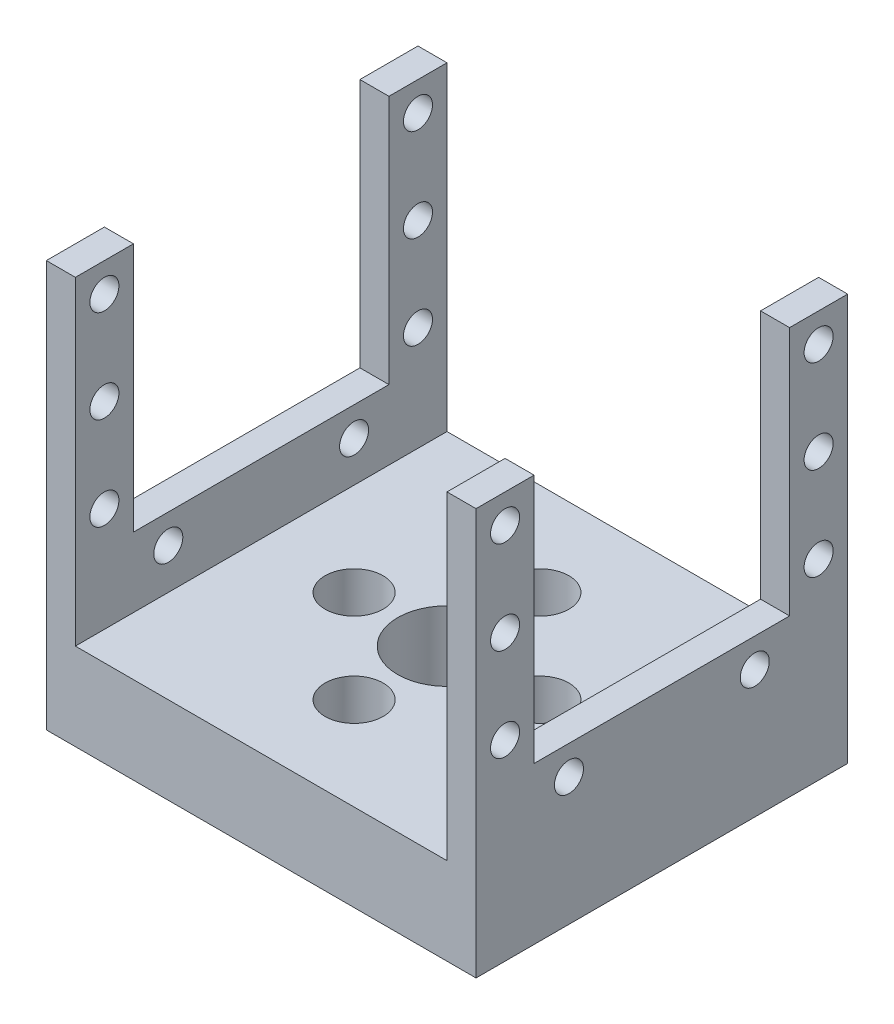
SolidWorks part; units mm, degrees
ref_plane "Front Plane" through (0, 0, 0) normal (0, 0, 1) x (1, 0, 0)
ref_plane "Top Plane" through (0, 0, 0) normal (0, 1, 0) x (1, 0, 0)
ref_plane "Right Plane" through (0, 0, 0) normal (1, 0, 0) x (0, 0, -1)
sketch "Sketch1" plane through (0, 0, 0) normal (0, 1, 0) x (1, 0, 0)
  line L1 (-18.5, -16) -> (18.5, -16)
  line L2 (-18.5, -16) -> (-18.5, 16)
  line L3 (-18.5, 16) -> (18.5, 16)
  line L4 (18.5, -16) -> (18.5, 16)
  line L5 (-18.5, -16) -> (18.5, 16) construction
  line L6 (-18.5, 16) -> (18.5, -16) construction
  point P0 (0, 0)
  dimension "D1" = 32
  dimension "D2" = 37
extrude "Boss-Extrude1" add sketch "Sketch1" along normal blind 35 contours L3 L4 L1 L2
sketch "Sketch2" plane through (-18.5, 0, 0) normal (-1, 0, 0) x (0, 0, 1)
  line L0 (-11, 35) -> (-11, 13.5)
  line L1 (16, 35) -> (-16, 35) construction
  line L2 (-11, 13.5) -> (11, 13.5)
  line L3 (11, 13.5) -> (11, 35)
  line L4 (11, 35) -> (-11, 35)
  line L5 (-13.5, 35) -> (-13.5, 13.5) construction
  line L6 (13.5, 35) -> (13.5, 13.5) construction
  line L7 (-16, 35) -> (-11, 35) construction
  line L8 (11, 35) -> (16, 35) construction
  circle A0 centre (-13.5, 32.5) radius 1.25
  circle A1 centre (-13.5, 24.5) radius 1.25
  circle A2 centre (-13.5, 16.5) radius 1.25
  circle A3 centre (-8, 11) radius 1.25
  circle A4 centre (8, 11) radius 1.25
  circle A5 centre (13.5, 32.5) radius 1.25
  circle A6 centre (13.5, 24.5) radius 1.25
  circle A7 centre (13.5, 16.5) radius 1.25
  point P27 (13.5, 35)
  point P31 (-13.5, 35)
  dimension "D1" = 5
  dimension "D3" = 2.5
  dimension "D2" = 5
  dimension "D4" = 2.5
  dimension "D5" = 8
  dimension "D6" = 8
  dimension "D7" = 5.5
  dimension "D8" = 5.5
  dimension "D9" = 2.5
  dimension "D10" = 16
extrude "Cut-Extrude1" cut sketch "Sketch2" against normal through all
sketch "Sketch3" plane through (0, 0, 16) normal (0, 0, 1) x (1, 0, 0)
  line L0 (-18.5, 35) -> (18.5, 35) construction
  line L1 (-16, 35) -> (16, 35)
  line L2 (-16, 35) -> (-16, 7.5)
  line L3 (-16, 7.5) -> (16, 7.5)
  line L4 (16, 35) -> (16, 7.5)
  dimension "D1" = 32
  dimension "D2" = 2.5
  dimension "D3" = 27.5
extrude "Cut-Extrude2" cut sketch "Sketch3" against normal through all
sketch "Sketch4" plane through (0, 7.5, 0) normal (0, 1, 0) x (1, 0, 0)
  line L0 (0, 8) -> (0, 0) construction
  line L1 (0, 0) -> (8, 0) construction
  line L2 (0, -8) -> (0, 0) construction
  line L3 (0, 0) -> (-8, 0) construction
  circle A0 centre (0, 0) radius 4.25
  circle A1 centre (0, 8) radius 1.25
  circle A2 centre (8, 0) radius 1.25
  circle A3 centre (0, -8) radius 1.25
  circle A4 centre (-8, 0) radius 1.25
  dimension "D1" = 8
  dimension "D2" = 8.5
  dimension "D3" = 2.5
extrude "Cut-Extrude3" cut sketch "Sketch4" against normal through all
sketch "Sketch5" plane through (0, 7.5, 0) normal (0, 1, 0) x (1, 0, 0)
  circle A0 centre (0, 8) radius 2.5
  circle A1 centre (8, 0) radius 2.5
  circle A2 centre (0, -8) radius 2.5
  circle A3 centre (-8, 0) radius 2.5
  dimension "D1" = 5
extrude "Cut-Extrude4" cut sketch "Sketch5" against normal offset from surface (5 mm away) 2.5 up to face at (-8, 0, 1.25)
